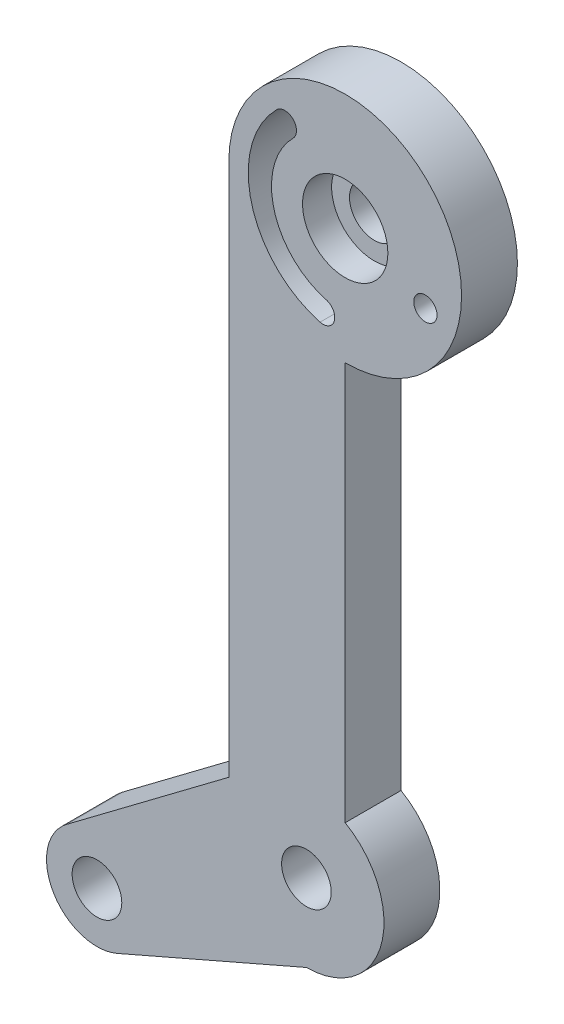
SolidWorks part; units mm, degrees
ref_plane "Front Plane" through (0, 0, 0) normal (0, 0, 1) x (1, 0, 0)
ref_plane "Top Plane" through (0, 0, 0) normal (0, 1, 0) x (1, 0, 0)
ref_plane "Right Plane" through (0, 0, 0) normal (1, 0, 0) x (0, 0, -1)
sketch "Sketch1" plane through (0, 0, 0) normal (0, 0, 1) x (1, 0, 0)
  line L0 (-5, 37.5) -> (-5, 3.1174)
  line L1 (2.5, 30) -> (2.5, 4.3301)
  line L2 (-12.2021, -10.3152) -> (0, -5)
  line L3 (-15.4525, -4.7374) -> (-5, 3.1174)
  circle A0 centre (0, 0) radius 1.6
  arc A1 (0, -5) -> (2.5, 4.3301) centre (0, 0) ccw
  circle A2 centre (-13.5, -7.3356) radius 1.6
  arc A3 (-15.4525, -4.7374) -> (-12.2021, -10.3152) centre (-13.5, -7.3356) ccw
  circle A4 centre (2.5, 37.5) radius 1.6
  arc A5 (2.5, 30) -> (-5, 37.5) centre (2.5, 37.5) ccw
  dimension "D1" = 3.2
  dimension "D4" = 5
  dimension "D5" = 3.25
  dimension "D6" = 7.5
  dimension "D7" = 12.2021
  dimension "D8" = 13.5
  dimension "D9" = 15.4525
  dimension "D10" = 30
extrude "Boss-Extrude1" add sketch "Sketch1" along normal blind 3.6
sketch "Sketch2" plane through (0, 0, 3.6) normal (0, 0, 1) x (1, 0, 0)
  line L0 (-5, 37.5) -> (-5, 3.1174) construction
  line L1 (2.5, 37.5) -> (-1.3891, 41.3891) construction
  line L2 (2.5, 37.5) -> (1.0765, 32.1874) construction
  line L3 (2.5, 37.5) -> (8, 37.5) construction
  line L4 (2.5, 37.5) -> (7.6683, 35.6189) construction
  circle A0 centre (7.6683, 35.6189) radius 0.75
  arc A1 (-0.8588, 40.8588) -> (-1.9194, 41.9194) centre (-1.3891, 41.3891) ccw
  arc A6 (0.8824, 31.463) -> (1.2706, 32.9119) centre (1.0765, 32.1874) ccw
  arc A7 (-1.9194, 41.9194) -> (0.8824, 31.463) centre (2.5, 37.5) ccw
  arc A8 (-0.8588, 40.8588) -> (1.2706, 32.9119) centre (2.5, 37.5) ccw
  dimension "D3" = 1.5
  dimension "D4" = 3.0806
  dimension "D2" = 120
  dimension "D1" = 6.25
  dimension "D5" = 20
extrude "Cut-Extrude1" cut sketch "Sketch2" against normal through all
sketch "Sketch3" [suppressed] plane through (0, 0, 0) normal (0, 0, -1) x (-1, 0, 0)
  circle A0 centre (-2.5, 37.5) radius 2.75
  dimension "D1" = 5.5
extrude "Cut-Extrude2" [suppressed] cut sketch "Sketch3" against normal blind 1.875
sketch "Sketch4" plane through (0, 0, 3.6) normal (0, 0, 1) x (1, 0, 0)
  circle A0 centre (2.5, 37.5) radius 2.75
  dimension "D1" = 5.5
extrude "Cut-Extrude3" cut sketch "Sketch4" against normal blind 1.875
